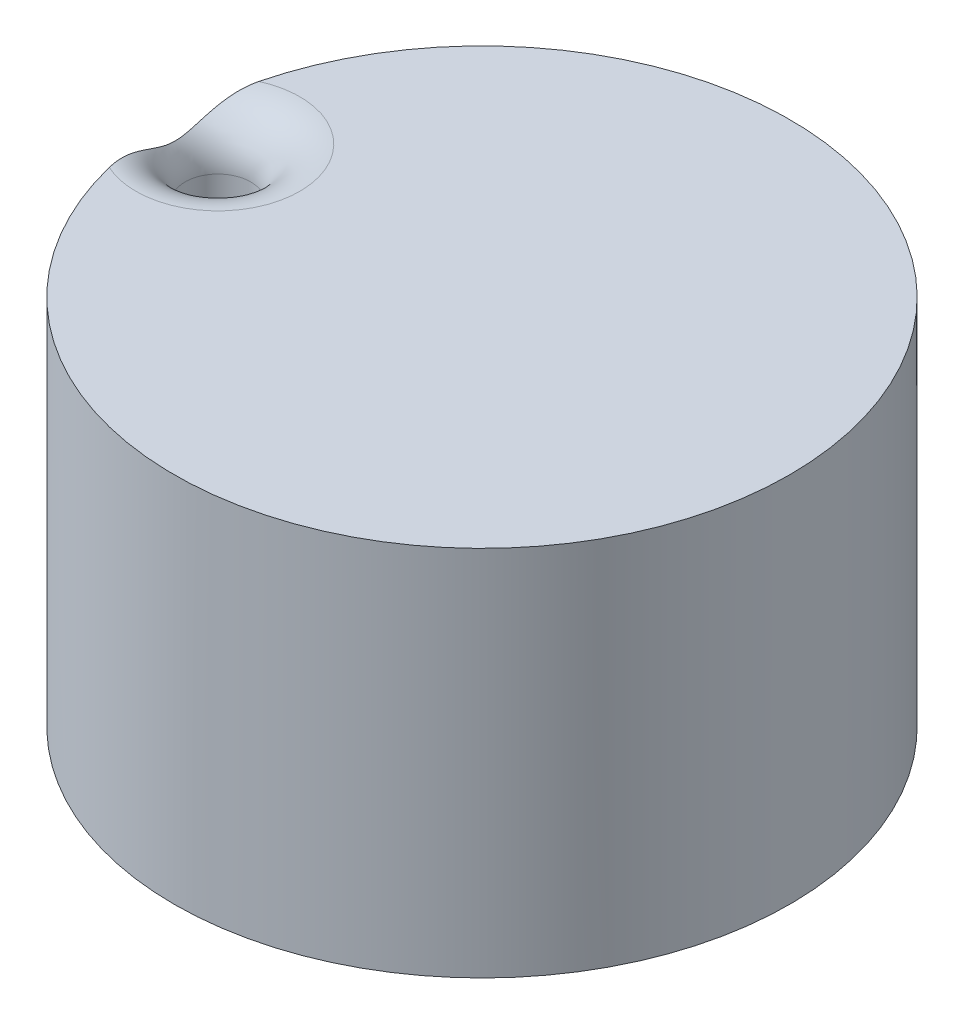
SolidWorks part; units mm, degrees
ref_plane "Front Plane" through (0, 0, 0) normal (0, 0, 1) x (1, 0, 0)
ref_plane "Top Plane" through (0, 0, 0) normal (0, 1, 0) x (1, 0, 0)
ref_plane "Right Plane" through (0, 0, 0) normal (1, 0, 0) x (0, 0, -1)
sketch "Sketch2" plane through (0, 0, 0) normal (0, 1, 0) x (1, 0, 0)
  circle A0 centre (0, 0) radius 47.6885
  dimension "D1" = 95.377
extrude "Boss-Extrude1" add sketch "Sketch2" along normal blind 57.658
sketch "Sketch3" plane through (0, 57.658, 0) normal (0, 1, 0) x (1, 0, 0)
  circle A1 centre (-41.0118, 0.0886) radius 5.08
extrude "Cut-Extrude1" cut sketch "Sketch3" against normal blind 57.658 contours A1
fillet "Fillet1" radius 7.62 1 edges at (-41.0118, 57.658, 4.9914)
sketch "Sketch4" plane through (0, 57.658, 0) normal (0, 1, 0) x (1, 0, 0)
  circle A1 centre (-26.162, 0) radius 3.175
  circle A2 centre (26.162, 0) radius 3.175
  circle A3 centre (0, 26.162) radius 3.175
  circle A4 centre (0, -26.162) radius 3.175
